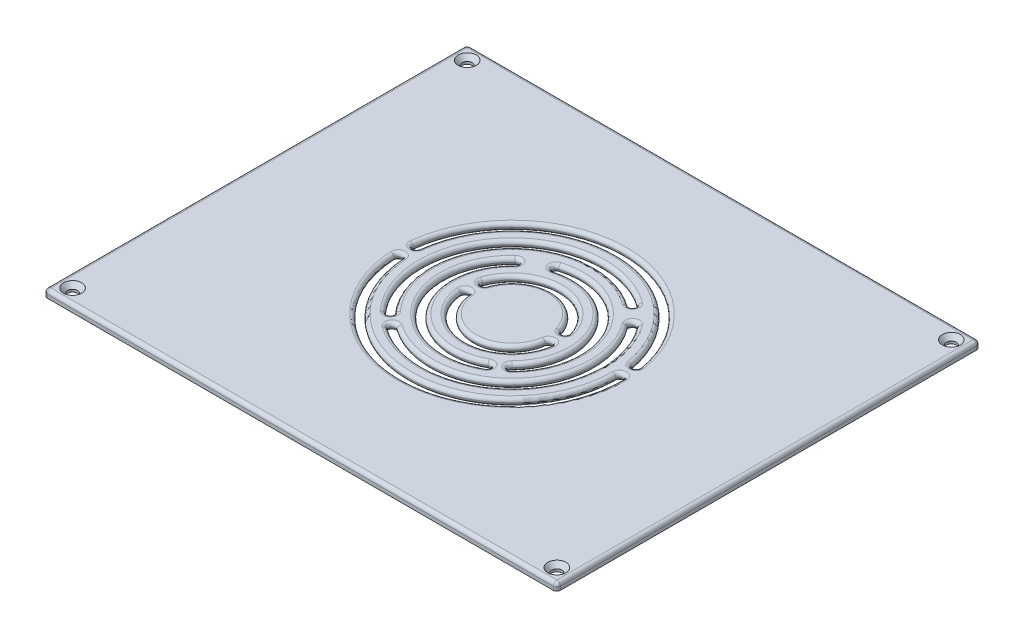
SolidWorks part; units mm, degrees
ref_plane "Front Plane" through (0, 0, 0) normal (0, 0, 1) x (1, 0, 0)
ref_plane "Top Plane" through (0, 0, 0) normal (0, 1, 0) x (1, 0, 0)
ref_plane "Right Plane" through (0, 0, 0) normal (1, 0, 0) x (0, 0, -1)
sketch "Sketch1" plane through (0, 0, 0) normal (0, 1, 0) x (1, 0, 0)
  line L1 (-71.5, 59) -> (71.5, 59)
  line L2 (-71.5, 59) -> (-71.5, -59)
  line L3 (-71.5, -59) -> (71.5, -59)
  line L4 (71.5, 59) -> (71.5, -59)
  line L5 (-71.5, 59) -> (71.5, -59) construction
  line L6 (-71.5, -59) -> (71.5, 59) construction
  point P0 (0, 0)
extrude "Boss-Extrude1" add sketch "Sketch1" along normal blind 2
sketch "Sketch2" plane through (0, 2, 0) normal (0, 1, 0) x (1, 0, 0)
  line L0 (-71.5, 59) -> (-71.5, -59) construction
  line L1 (71.5, 59) -> (-71.5, 59) construction
  line L2 (-71.5, -59) -> (71.5, -59) construction
  line L3 (71.5, -59) -> (71.5, 59) construction
  point P0 (-67.5, 55)
  point P1 (-54, 55)
  point P2 (67.5, -55)
  point P3 (-67.5, -55)
  point P8 (67.5, 55)
  dimension "D1" = 4
  dimension "D2" = 4
  dimension "D3" = 4
  dimension "D4" = 4
  dimension "D5" = 4
  dimension "D6" = 4
  dimension "D7" = 4
  dimension "D8" = 4
hole_wizard "CSK for #3 Flat Head Machine Screw1" positions "3DSketch3" profile "Sketch7" countersink size "#3" standard "ANSI Inch" end condition through all
sketch3d "3DSketch3"
  point P0 (67.5, 2, 55)
  point P3 (-67.5, 2, 55)
  point P6 (-67.5, 2, -55)
  point P9 (67.5, 2, -55)
sketch "Sketch7" plane through (67.5, 2, 55) normal (1, 0, 0) x (0, 0, 1)
  line L0 (0, 0) -> (0, 2)
  line L1 (0, 2) -> (1.397, 2)
  line L2 (1.397, 2) -> (1.397, 1.3003)
  line L3 (1.397, 1.3003) -> (2.5273, 0)
  line L5 (2.5273, 0) -> (0, 0)
  line L6 (-1.397, 1.3003) -> (-2.5273, 0) construction
  line L11 (0, -6.35) -> (0, 107.95) construction
  dimension "Thru Hole Dia." = 2.794
  dimension "Thru Hole Depth" = 2
  dimension "Near C'Sink Dia." = 5.0546
  dimension "Near C'Sink Angle" = 82
sketch "Sketch8" plane through (0, 2, 0) normal (0, 1, 0) x (1, 0, 0)
  arc A0 (-29.9482, -1.7671) -> (30.0003, 0) centre (0, 0) ccw construction
  arc A9 (-30.9464, -1.826) -> (31.0003, 0) centre (0, 0) ccw
  arc A10 (-28.9499, -1.7082) -> (29.0003, 0) centre (0, 0) ccw
  arc A11 (-28.9499, -1.7082) -> (-30.9464, -1.826) centre (-29.9482, -1.7671) ccw
  arc A12 (31.0003, 0) -> (29.0003, 0) centre (30.0003, 0) ccw
  arc A13 (-29.8256, 3.2329) -> (29.5807, 5) centre (0, 0) cw construction
  arc A14 (30.5667, 5.1667) -> (-30.8197, 3.3406) centre (0, 0) ccw
  arc A15 (28.5947, 4.8333) -> (-28.8314, 3.1251) centre (0, 0) ccw
  arc A16 (28.5947, 4.8333) -> (30.5667, 5.1667) centre (29.5807, 5) ccw
  arc A17 (-30.8197, 3.3406) -> (-28.8314, 3.1251) centre (-29.8256, 3.2329) ccw
  arc A18 (-17.6186, -16.2972) -> (14.2946, 19.2789) centre (0, 0) cw construction
  arc A19 (14.8902, 20.0822) -> (-18.3527, -16.9762) centre (0, 0) ccw
  arc A20 (13.699, 18.4756) -> (-16.8845, -15.6181) centre (0, 0) ccw
  arc A21 (13.699, 18.4756) -> (14.8902, 20.0822) centre (14.2946, 19.2789) ccw
  arc A22 (-18.3527, -16.9762) -> (-16.8845, -15.6181) centre (-17.6186, -16.2972) ccw
  arc A23 (19.2946, 14.2734) -> (-13.8595, -19.5941) centre (0, 0) cw construction
  arc A24 (-14.437, -20.4105) -> (20.0985, 14.8681) centre (0, 0) ccw
  arc A25 (-13.282, -18.7776) -> (18.4907, 13.6787) centre (0, 0) ccw
  arc A26 (-13.282, -18.7776) -> (-14.437, -20.4105) centre (-13.8595, -19.5941) ccw
  arc A27 (20.0985, 14.8681) -> (18.4907, 13.6787) centre (19.2946, 14.2734) ccw
  arc A28 (12.7017, -12.7545) -> (-5, 17.2919) centre (0, 0) ccw construction
  arc A29 (13.4073, -13.4631) -> (-5.2778, 18.2525) centre (0, 0) ccw
  arc A30 (11.996, -12.0459) -> (-4.7222, 16.3313) centre (0, 0) ccw
  arc A31 (11.996, -12.0459) -> (13.4073, -13.4631) centre (12.7017, -12.7545) ccw
  arc A32 (-5.2778, 18.2525) -> (-4.7222, 16.3313) centre (-5, 17.2919) ccw
  arc A33 (8.7031, -15.7564) -> (-12.3472, 13.098) centre (0, 0) cw construction
  arc A34 (-13.0331, 13.8257) -> (9.1866, -16.6318) centre (0, 0) ccw
  arc A35 (-11.6612, 12.3703) -> (8.2196, -14.8811) centre (0, 0) ccw
  arc A36 (-11.6612, 12.3703) -> (-13.0331, 13.8257) centre (-12.3472, 13.098) ccw
  arc A37 (9.1866, -16.6318) -> (8.2196, -14.8811) centre (8.7031, -15.7564) ccw
  arc A38 (-11.3869, 3.7875) -> (11.5454, 3.2727) centre (0, 0) cw construction
  arc A39 (12.5075, 3.5454) -> (-12.3358, 4.1031) centre (0, 0) ccw
  arc A40 (10.5833, 3) -> (-10.438, 3.4718) centre (0, 0) ccw
  arc A41 (10.5833, 3) -> (12.5075, 3.5454) centre (11.5454, 3.2727) ccw
  arc A42 (-12.3358, 4.1031) -> (-10.438, 3.4718) centre (-11.3869, 3.7875) ccw
  arc A43 (11.8753, -1.7273) -> (-11.9389, -1.2125) centre (0, 0) cw construction
  arc A44 (-12.9337, -1.3136) -> (12.8649, -1.8713) centre (0, 0) ccw
  arc A45 (-10.944, -1.1115) -> (10.8857, -1.5834) centre (0, 0) ccw
  arc A46 (-10.944, -1.1115) -> (-12.9337, -1.3136) centre (-11.9389, -1.2125) ccw
  arc A47 (12.8649, -1.8713) -> (10.8857, -1.5834) centre (11.8753, -1.7273) ccw
  arc A66 (0.0003, -0.0001) -> (-0.0001, 0.0003) centre (0, 0) ccw construction
  arc A76 (0.0004, -0.0002) -> (-0.0001, 0.0004) centre (0, 0) ccw
  arc A77 (0.0001, -0.0001) -> (0, 0.0001) centre (0, 0) ccw
  arc A78 (0.0001, -0.0001) -> (0.0004, -0.0002) centre (0.0003, -0.0001) ccw
  arc A79 (-0.0001, 0.0004) -> (0, 0.0001) centre (-0.0001, 0.0003) ccw
  point P4 (0.8839, -29.9872)
  point P14 (-0.892, 29.987)
  point P22 (-17.8655, 16.0261)
  point P28 (17.1504, -16.7892)
  point P36 (15.5089, 9.137)
  point P44 (-14.5418, -10.6087)
  point P52 (0.2693, 11.9972)
  point P60 (-0.2593, -11.9975)
  point P84 (0.0002, 0.0002)
  dimension "D1" = 6
  dimension "D2" = 6
  dimension "D3" = 6
  dimension "D4" = 6
  dimension "D5" = 6
  dimension "D6" = 6
  dimension "D7" = 5
  dimension "D9" = 5
  dimension "D8" = 6
  dimension "D10" = 5
  dimension "D11" = 5
  dimension "D12" = 5
  dimension "D13" = 5
  dimension "D14" = 5
  dimension "D15" = 5
extrude "Cut-Extrude1" cut sketch "Sketch8" against normal blind 2
fillet "Fillet2" radius 1 4 edges at (-11.6195, 2, -13.7839) (-13.734, 2, 10.0194) (9.5785, 2, 15.2729) (-15.3497, 2, 11.1981)
fillet "Fillet3" radius 1 4 edges at (29.7473, 2, -4.014) (-0.9217, 2, -30.9866) (-29.9333, 2, -2.2387) (-0.8623, 2, -28.9874)
fillet "Fillet4" radius 1 4 edges at (-0.9217, 0, -30.9866) (29.7473, 0, -4.014) (-0.8623, 0, -28.9874) (-29.9333, 0, -2.2387)
fillet "Fillet5" radius 1 4 edges at (14.6473, 0, -8.6294) (-5.9606, 0, -17.0141) (16.3705, 0, -9.6446) (11.9931, 0, 13.4601)
fillet "Fillet6" radius 1 4 edges at (15.0979, 2, -18.6833) (-18.6099, 2, -16.6938) (-16.9395, 2, 17.0313) (-17.1211, 2, -15.3584)
fillet "Fillet7" radius 1 4 edges at (-17.1211, 0, -15.3584) (-16.9395, 0, 17.0313) (-18.6099, 0, -16.6938) (15.0979, 0, -18.6833)
fillet "Fillet8" radius 1 4 edges at (-0.281, 0, 12.9972) (-12.0399, 0, 0.2177) (-0.2377, 0, 10.9977) (12.0192, 0, 0.7377)
fillet "Fillet9" radius 1 4 edges at (9.5785, 0, 15.2729) (-13.734, 0, 10.0194) (-15.3497, 0, 11.1981) (-11.6195, 0, -13.7839)
fillet "Fillet10" radius 1 4 edges at (-0.281, 2, 12.9972) (12.0192, 2, 0.7377) (-0.2377, 2, 10.9977) (-12.0399, 2, 0.2177)
fillet "Fillet11" radius 1 4 edges at (-30.0071, 0, 0.7689) (0.8545, 0, 28.9877) (30.0003, 0, -1) (0.9134, 0, 30.9868)
fillet "Fillet12" radius 1 4 edges at (-14.6759, 2, 19.0166) (17.865, 2, 17.4887) (18.6999, 2, -15.0774) (16.4358, 2, 16.0896)
fillet "Fillet13" radius 1 4 edges at (11.8181, 2, -2.3106) (0.2918, 2, -12.997) (-11.7025, 2, -2.8386) (0.2469, 2, -10.9975)
fillet "Fillet14" radius 1 4 edges at (11.8181, 0, -2.3106) (0.2469, 0, -10.9975) (-11.7025, 0, -2.8386) (0.2918, 0, -12.997)
fillet "Fillet15" radius 1 8 edges at (16.3705, 2, -9.6446) (-5.9606, 2, -17.0141) (14.6473, 2, -8.6294) (11.9931, 2, 13.4601) (0.9134, 2, 30.9868) (30.0003, 2, -1) (0.8545, 2, 28.9877) (-30.0071, 2, 0.7689)
fillet "Fillet16" radius 1 4 edges at (-14.6759, 0, 19.0166) (18.6999, 0, -15.0774) (16.4358, 0, 16.0896) (17.865, 0, 17.4887)
fillet "Fillet17" radius 1 8 edges at (0, 2, 59) (-71.5, 2, 0) (0, 2, -59) (71.5, 2, 0) (71.5, 1, -59) (-71.5, 1, -59) (-71.5, 1, 59) (71.5, 1, 59)
